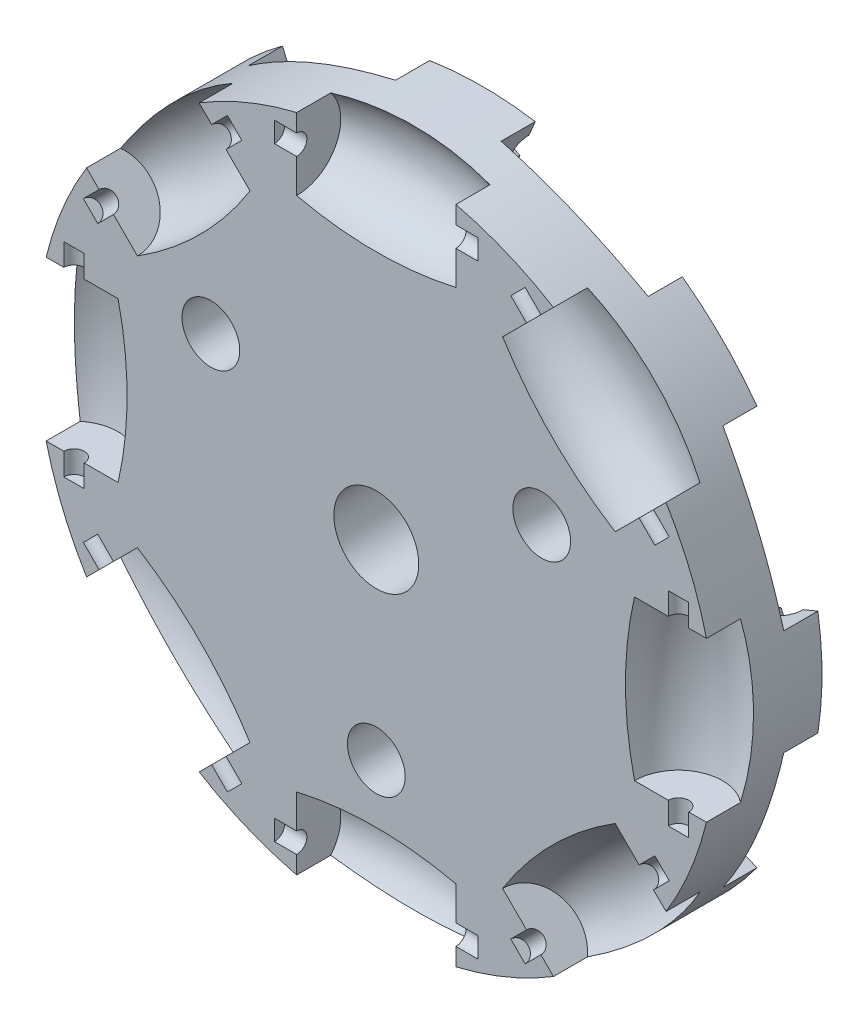
SolidWorks part; units mm, degrees
ref_plane "Front Plane" through (0, 0, 0) normal (0, 0, 1) x (1, 0, 0)
ref_plane "Top Plane" through (0, 0, 0) normal (0, 1, 0) x (1, 0, 0)
ref_plane "Right Plane" through (0, 0, 0) normal (1, 0, 0) x (0, 0, -1)
sketch "Sketch1" plane through (0, 0, 0) normal (0, 0, 1) x (1, 0, 0)
  circle A0 centre (0, 0) radius 25.4
  point P11 (0, 0)
  dimension "D1" = 50.8
extrude "Boss-Extrude1" add sketch "Sketch1" along normal mid plane 7.9375
ref_plane "Plane1" through (0, 0, 3.9688) normal (0, 0, 1) x (1, 0, 0)
ref_plane "Plane2" through (0, 0, -3.9688) normal (0, 0, 1) x (1, 0, 0)
sketch "Sketch5" plane through (0, 0, 3.9688) normal (0, 0, 1) x (1, 0, 0)
  line L0 (-5.9531, 25.8994) -> (-5.9531, 22.606)
  line L1 (-5.9531, 22.606) -> (5.9531, 22.606)
  line L2 (5.9531, 22.606) -> (5.9531, 25.8994)
  line L3 (-5.9531, 22.606) -> (-8.0326, 22.606) construction
  arc A2 (-5.9531, 25.8994) -> (5.9531, 25.8994) centre (0, 0) cw
  point P2 (0, 26.5748)
  point P7 (0, 22.606)
  dimension "D1" = 11.9062
  dimension "D2" = 7.9375
  dimension "D3" = 22.606
revolve "Cut-Revolve5" cut sketch "Sketch5" angle 360 about L1
sketch "Sketch8" plane through (0, 0, -3.9688) normal (0, 0, 1) x (1, 0, 0)
  line L0 (4.4113, 26.2061) -> (3.151, 23.1634)
  line L1 (3.151, 23.1634) -> (14.1509, 18.6071)
  line L2 (14.1509, 18.6071) -> (15.4112, 21.6497)
  line L3 (3.151, 23.1634) -> (-2.0499, 25.3177) construction
  line L4 (0, 0) -> (9.7202, 23.4665) construction
  line L5 (0, 0) -> (0, 7.8748) construction
  arc A0 (4.4113, 26.2061) -> (15.4112, 21.6497) centre (0, 0) cw
  arc A2 (-5.9531, 24.6925) -> (5.9531, 24.6925) centre (0, 0) ccw construction
  point P6 (8.6509, 20.8852)
  point P14 (10.1697, 24.5519)
  dimension "D1" = 11.9062
  dimension "D2" = 7.9375
  dimension "D3" = 22.5
  dimension "D4" = 22.606
revolve "Cut-Revolve6" cut sketch "Sketch8" angle 360 about L3
sketch "Sketch6" plane through (0, 0, 0) normal (1, 0, 0) x (0, 0, -1)
  arc A0 (-3.9688, 19.3126) -> (-1.4207, 24.6925) centre (-3.9688, 22.606) ccw construction
  circle A1 centre (-3.9688, 22.606) radius 0.762
  point P4 (-3.9688, 22.606)
  dimension "D1" = 1.524
extrude "Cut-Extrude2" cut sketch "Sketch6" against normal mid plane 15.24
ref_axis "Axis1" through (0, 0, -8.8615) along (0, 0, 1)
ref_plane "Plane3" through (0, 0, 0) normal (0.9239, -0.3827, 0) x (0, 0, -1)
sketch "Sketch10" plane through (0, 0, 0) normal (0.9239, -0.3827, 0) x (0, 0, -1)
  arc A1 (1.4207, 24.6925) -> (3.9688, 19.3126) centre (3.9688, 22.606) ccw construction
  circle A2 centre (3.9688, 22.606) radius 0.889
  point P4 (3.9688, 22.606)
  dimension "D1" = 1.778
extrude "Cut-Extrude3" cut sketch "Sketch10" against normal mid plane 15.875
pattern_circular "CirPattern1" count 8 over 360 about axis through (0, 0, 3.9688) along (0, 0, -1) of "Cut-Revolve5", "Cut-Revolve6", "Cut-Extrude2", "Cut-Extrude3"
sketch "Sketch16" plane through (0, 0, 3.9688) normal (0, 0, 1) x (1, 0, 0)
  circle A0 centre (0, -14.2875) radius 2.159
  circle A1 centre (-12.3733, 7.1437) radius 2.159
  circle A2 centre (12.3733, 7.1438) radius 2.159
  point P9 (0, 0)
  dimension "D1" = 4.318
  dimension "D2" = 14.2875
  dimension "D3" = 3
extrude "Cut-Extrude7" cut sketch "Sketch16" against normal through all
sketch "Sketch17" plane through (0, 0, 3.9688) normal (0, 0, 1) x (1, 0, 0)
  circle A0 centre (0, 0) radius 3.175
  dimension "D1" = 6.35
extrude "Cut-Extrude8" cut sketch "Sketch17" against normal through all
